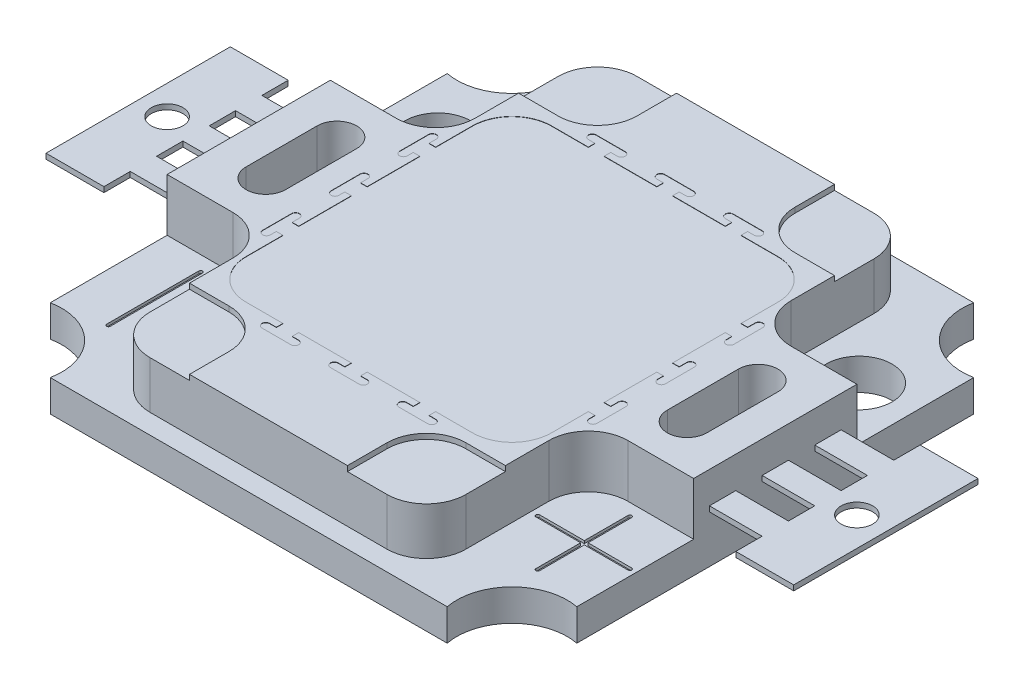
SolidWorks part; units mm, degrees
ref_plane "Front" through (0, 0, 0) normal (0, 0, 1) x (1, 0, 0)
ref_plane "Top" through (0, 0, 0) normal (0, 1, 0) x (1, 0, 0)
ref_plane "Right" through (0, 0, 0) normal (1, 0, 0) x (0, 0, -1)
sketch "Sketch1" plane through (0, 0, 0) normal (0, 1, 0) x (1, 0, 0)
  line L1 (0, 0) -> (20, 0)
  line L2 (0, 0) -> (0, 20)
  line L3 (0, 20) -> (20, 20)
  line L4 (20, 0) -> (20, 20)
  dimension "D1" = 20
  dimension "D2" = 20
extrude "Boss-Extrude1" add sketch "Sketch1" along normal blind 1.2
sketch "Sketch3" plane through (0, 1.2, 0) normal (0, 1, 0) x (1, 0, 0)
  line L0 (4, 19.25) -> (16, 0.75) construction
  line L1 (4, 19.25) -> (16, 19.25)
  line L2 (4, 19.25) -> (4, 13.1)
  line L3 (4, 0.75) -> (16, 0.75)
  line L4 (16, 19.25) -> (16, 13.1)
  line L5 (20, 20) -> (0, 0) construction
  line L6 (10, 10) -> (26, 10) construction
  line L7 (20, 0) -> (20, 20) construction
  line L8 (20, 6.9) -> (16, 6.9)
  line L9 (20, 6.9) -> (20, 13.1)
  line L10 (20, 13.1) -> (16, 13.1)
  line L11 (10, 10) -> (10, 16.9399) construction
  line L12 (16, 6.9) -> (20, 13.1) construction
  line L13 (16, 6.9) -> (16, 0.75)
  line L14 (0, 13.1) -> (4, 13.1)
  line L15 (0, 6.9) -> (0, 13.1)
  line L16 (0, 6.9) -> (4, 6.9)
  line L17 (4, 6.9) -> (4, 0.75)
  line L18 (18, 8.65) -> (18, 11.35) construction
  line L19 (18, 13.1) -> (18, 6.9) construction
  line L20 (17.25, 8.65) -> (17.25, 11.35)
  line L21 (18.75, 8.65) -> (18.75, 11.35)
  line L22 (16.5912, 12.1) -> (19.137, 12.1) construction
  line L23 (2, 8.65) -> (2, 11.35) construction
  line L24 (2.75, 8.65) -> (2.75, 11.35)
  line L25 (1.25, 8.65) -> (1.25, 11.35)
  line L26 (6, 4.95) -> (14, 15.05) construction
  line L27 (6, 15.05) -> (14, 15.05)
  line L28 (6, 15.05) -> (6, 4.95)
  line L29 (6, 4.95) -> (14, 4.95)
  line L30 (14, 15.05) -> (14, 4.95)
  arc A0 (17.25, 8.65) -> (18.75, 8.65) centre (18, 8.65) ccw
  arc A1 (18.75, 11.35) -> (17.25, 11.35) centre (18, 11.35) ccw
  arc A2 (2.75, 8.65) -> (1.25, 8.65) centre (2, 8.65) cw
  arc A3 (1.25, 11.35) -> (2.75, 11.35) centre (2, 11.35) cw
  point P8 (10, 10)
  point P17 (18, 10)
  point P27 (18, 10)
  point P36 (2, 10)
  dimension "D5" = 1
  dimension "D1" = 18.5
  dimension "D2" = 12
  dimension "D3" = 6.2
  dimension "D4" = 4.2
  dimension "D6" = 1.5
  dimension "D7" = 6
extrude "Boss-Extrude2" add sketch "Sketch3" along normal blind 2
sketch "Sketch4" plane through (0, 3.2, 0) normal (0, 1, 0) x (1, 0, 0)
  line L0 (20, 6.9) -> (20, 13.1) construction
  line L1 (4.2, 15.8) -> (15.8, 15.8)
  line L2 (4.2, 15.8) -> (4.2, 4.2)
  line L3 (4.2, 4.2) -> (15.8, 4.2)
  line L4 (15.8, 15.8) -> (15.8, 4.2)
  line L5 (0, 13.1) -> (0, 6.9) construction
  line L6 (0, 0) -> (20, 0) construction
  line L7 (20, 20) -> (0, 20) construction
  line L9 (4, 0.75) -> (7, 0.75)
  line L10 (4, 0.75) -> (4, 3.75)
  line L11 (4, 3.75) -> (7, 3.75)
  line L12 (7, 0.75) -> (7, 3.75)
  line L13 (16, 19.25) -> (13, 19.25)
  line L14 (16, 19.25) -> (16, 16.25)
  line L15 (16, 16.25) -> (13, 16.25)
  line L16 (13, 19.25) -> (13, 16.25)
  line L17 (4, 19.25) -> (7, 19.25)
  line L18 (4, 19.25) -> (4, 16.25)
  line L19 (4, 16.25) -> (7, 16.25)
  line L20 (7, 19.25) -> (7, 16.25)
  line L21 (16, 0.75) -> (13, 0.75)
  line L22 (16, 0.75) -> (16, 3.75)
  line L23 (16, 3.75) -> (13, 3.75)
  line L24 (13, 0.75) -> (13, 3.75)
  dimension "D1" = 4.2
  dimension "D2" = 4.2
  dimension "D3" = 4.2
  dimension "D4" = 4.2
  dimension "D5" = 3
fillet "Fillet1" radius 1.5 8 edges at (4, 2.2, -13.1) (4, 2.2, -6.9) (16, 2.2, -13.1) (16, 2.2, -6.9) (4, 2.2, -19.25) (16, 2.2, -19.25) (4, 2.2, -0.75) (16, 2.2, -0.75)
extrude "Cut-Extrude1" cut sketch "Sketch4" against normal blind 0.2
fillet "Fillet2" radius 1.5 8 edges at (13, 3.1, -16.25) (7, 3.1, -16.25) (7, 3.1, -3.75) (13, 3.1, -3.75) (15.8, 3.1, -4.2) (4.2, 3.1, -4.2) (4.2, 3.1, -15.8) (15.8, 3.1, -15.8)
sketch "Sketch5" plane through (0, 1.2, 0) normal (0, 1, 0) x (1, 0, 0)
  line L0 (20, 20) -> (0, 20) construction
  line L13 (0.4, 19.6) -> (19.6, 19.6) construction
  line L14 (0.4, 19.6) -> (0.4, 0.4) construction
  line L15 (0.4, 0.4) -> (19.6, 0.4) construction
  line L16 (19.6, 19.6) -> (19.6, 0.4) construction
  line L17 (20, 13.1) -> (20, 20) construction
  line L18 (0, 6.9) -> (0, 0) construction
  line L19 (0, 0) -> (20, 0) construction
  line L20 (2.5, 22.6773) -> (2.5, 16.8106) construction
  line L21 (0, 20) -> (0, 13.1) construction
  circle A0 centre (0.4, 19.6) radius 2.1
  dimension "D1" = 0.4
  dimension "D2" = 0.4
  dimension "D3" = 0.4
  dimension "D4" = 0.4
  dimension "D5" = 2.5
  dimension "D6" = 19.2
extrude "Cut-Extrude2" cut sketch "Sketch5" against normal through all
pattern_linear "LPattern1" count 2 spacing 19.2 along (1, 0, 0) count 2 spacing 19.2 along (0, 0, 1) of "Cut-Extrude2"
ref_plane "Plane1" through (0, 2, 0) normal (0, 1, 0) x (1, 0, 0)
sketch "Sketch6" plane through (0, 2, 0) normal (0, 1, 0) x (1, 0, 0)
  line L0 (20, 6.9) -> (20, 13.1) construction
  line L1 (22, 13.5) -> (24.2, 13.5)
  line L2 (22, 13.5) -> (22, 12.5)
  line L3 (22, 6.5) -> (24.2, 6.5)
  line L4 (24.2, 13.5) -> (24.2, 6.5)
  line L5 (20, 12.5) -> (22, 12.5)
  line L6 (20, 12.5) -> (20, 11.5)
  line L7 (20, 11.5) -> (22, 11.5)
  line L8 (22, 10.5) -> (22, 9.5) construction
  line L9 (22, 7.5) -> (22, 6.5)
  line L10 (20, 10.5) -> (22, 10.5)
  line L11 (20, 10.5) -> (20, 9.5)
  line L12 (20, 9.5) -> (22, 9.5)
  line L13 (22, 11.5) -> (22, 10.5)
  line L14 (20, 8.5) -> (22, 8.5)
  line L15 (20, 8.5) -> (20, 7.5)
  line L16 (20, 7.5) -> (22, 7.5)
  line L17 (22, 9.5) -> (22, 8.5)
  line L18 (20, 10) -> (24.2, 10) construction
  line L19 (10, 0.75) -> (10, 19.25) construction
  line L20 (5.5, 0.75) -> (14.5, 0.75) construction
  line L21 (13, 19.25) -> (7, 19.25) construction
  line L22 (23.1, 13.5) -> (23.1, 6.5) construction
  line L23 (-3.1, 13.5) -> (-3.1, 6.5) construction
  line L24 (0, 10) -> (-4.2, 10) construction
  line L25 (-2, 10.5) -> (-2, 9.5) construction
  line L26 (-2, 9.5) -> (-2, 8.5)
  line L27 (0, 7.5) -> (-2, 7.5)
  line L28 (0, 8.5) -> (0, 7.5)
  line L29 (0, 8.5) -> (-2, 8.5)
  line L30 (-2, 11.5) -> (-2, 10.5)
  line L31 (0, 9.5) -> (-2, 9.5)
  line L32 (0, 10.5) -> (0, 9.5)
  line L33 (0, 10.5) -> (-2, 10.5)
  line L34 (-2, 7.5) -> (-2, 6.5)
  line L35 (0, 11.5) -> (-2, 11.5)
  line L36 (0, 12.5) -> (0, 11.5)
  line L37 (0, 12.5) -> (-2, 12.5)
  line L38 (-4.2, 13.5) -> (-4.2, 6.5)
  line L39 (-2, 6.5) -> (-4.2, 6.5)
  line L40 (-2, 13.5) -> (-2, 12.5)
  line L41 (-2, 13.5) -> (-4.2, 13.5)
  circle A0 centre (23.1, 10) radius 0.6
  circle A1 centre (-3.1, 10) radius 0.6
  dimension "D9" = 1.2
  dimension "D1" = 7
  dimension "D2" = 2.2
  dimension "D3" = 2
  dimension "D4" = 1
  dimension "D5" = 1
  dimension "D6" = 1
  dimension "D7" = 1
  dimension "D8" = 1
extrude "Boss-Extrude3" add sketch "Sketch6" against normal blind 0.2
sketch "Sketch7" plane through (0, 3.2, 0) normal (0, 1, 0) x (1, 0, 0)
  line L0 (4.7825, 3.8) -> (14.632, 3.8) construction
  line L1 (5.7, 4.2) -> (14.3, 4.2) construction
  line L2 (9.45, 3.8) -> (10.55, 3.8) construction
  line L3 (9.45, 3.95) -> (9.7, 3.95)
  line L4 (9.45, 3.65) -> (10.55, 3.65)
  line L5 (9.3, 4.0517) -> (9.3, 3.1833) construction
  line L6 (10.7, 4.0517) -> (10.7, 3.1833) construction
  line L7 (10, 4.2) -> (10, 3.4) construction
  line L8 (12.05, 3.95) -> (12.3, 3.95)
  line L9 (12.05, 3.65) -> (13.15, 3.65)
  line L10 (5.7, 4.2) -> (14.3, 4.2) construction
  line L11 (12.9, 4.2) -> (12.3, 4.2)
  line L12 (12.9, 4.2) -> (12.9, 3.95)
  line L13 (12.3, 4.2) -> (12.3, 3.95)
  line L14 (12.9, 3.95) -> (13.15, 3.95)
  line L15 (12.05, 3.8) -> (13.15, 3.8) construction
  line L16 (6.85, 3.95) -> (7.1, 3.95)
  line L17 (6.85, 3.65) -> (7.95, 3.65)
  line L18 (7.7, 4.2) -> (7.1, 4.2)
  line L19 (7.7, 4.2) -> (7.7, 3.95)
  line L20 (10.3, 4.2) -> (9.7, 4.2)
  line L21 (10.3, 4.2) -> (10.3, 3.95)
  line L22 (7.1, 4.2) -> (7.1, 3.95)
  line L23 (9.7, 4.2) -> (9.7, 3.95)
  line L24 (10.3, 3.95) -> (10.55, 3.95)
  line L25 (7.7, 3.95) -> (7.95, 3.95)
  line L26 (6.85, 3.8) -> (7.95, 3.8) construction
  line L27 (6, 10) -> (14, 10) construction
  line L28 (6, 15.05) -> (6, 4.95) construction
  line L29 (14, 4.95) -> (14, 15.05) construction
  line L30 (6.85, 16.2) -> (7.95, 16.2) construction
  line L31 (12.05, 16.2) -> (13.15, 16.2) construction
  line L32 (10, 15.8) -> (10, 16.6) construction
  line L33 (10.7, 15.9483) -> (10.7, 16.8167) construction
  line L34 (9.3, 15.9483) -> (9.3, 16.8167) construction
  line L35 (9.45, 16.2) -> (10.55, 16.2) construction
  line L36 (7.7, 16.05) -> (7.95, 16.05)
  line L37 (10.3, 16.05) -> (10.55, 16.05)
  line L38 (9.7, 15.8) -> (9.7, 16.05)
  line L39 (7.1, 15.8) -> (7.1, 16.05)
  line L40 (10.3, 15.8) -> (10.3, 16.05)
  line L41 (10.3, 15.8) -> (9.7, 15.8)
  line L42 (7.7, 15.8) -> (7.7, 16.05)
  line L43 (7.7, 15.8) -> (7.1, 15.8)
  line L44 (6.85, 16.35) -> (7.95, 16.35)
  line L45 (6.85, 16.05) -> (7.1, 16.05)
  line L46 (12.9, 16.05) -> (13.15, 16.05)
  line L47 (12.3, 15.8) -> (12.3, 16.05)
  line L48 (12.9, 15.8) -> (12.9, 16.05)
  line L49 (12.9, 15.8) -> (12.3, 15.8)
  line L50 (12.05, 16.35) -> (13.15, 16.35)
  line L51 (12.05, 16.05) -> (12.3, 16.05)
  line L52 (9.45, 16.35) -> (10.55, 16.35)
  line L53 (9.45, 16.05) -> (9.7, 16.05)
  arc A0 (9.45, 3.95) -> (9.45, 3.65) centre (9.45, 3.8) ccw
  arc A1 (10.55, 3.65) -> (10.55, 3.95) centre (10.55, 3.8) ccw
  arc A2 (12.05, 3.95) -> (12.05, 3.65) centre (12.05, 3.8) ccw
  arc A3 (13.15, 3.65) -> (13.15, 3.95) centre (13.15, 3.8) ccw
  arc A4 (6.85, 3.95) -> (6.85, 3.65) centre (6.85, 3.8) ccw
  arc A5 (7.95, 3.65) -> (7.95, 3.95) centre (7.95, 3.8) ccw
  arc A6 (7.95, 16.35) -> (7.95, 16.05) centre (7.95, 16.2) cw
  arc A7 (6.85, 16.05) -> (6.85, 16.35) centre (6.85, 16.2) cw
  arc A8 (13.15, 16.35) -> (13.15, 16.05) centre (13.15, 16.2) cw
  arc A9 (12.05, 16.05) -> (12.05, 16.35) centre (12.05, 16.2) cw
  arc A10 (10.55, 16.35) -> (10.55, 16.05) centre (10.55, 16.2) cw
  arc A11 (9.45, 16.05) -> (9.45, 16.35) centre (9.45, 16.2) cw
  point P6 (10, 3.8)
  point P22 (12.6, 3.8)
  point P35 (7.4, 3.8)
  point P87 (7.4, 16.2)
  point P88 (12.6, 16.2)
  point P89 (10, 16.2)
  dimension "D1" = 0.4
  dimension "D2" = 0.3
  dimension "D3" = 1.4
  dimension "D6" = 0.6
sketch "Sketch8" plane through (0, 3.2, 0) normal (0, 1, 0) x (1, 0, 0)
  line L0 (10, 15.05) -> (10, 4.95) construction
  line L1 (14, 15.05) -> (6, 15.05) construction
  line L2 (6, 4.95) -> (14, 4.95) construction
  line L3 (3.8, 14.7064) -> (3.8, 5.2936) construction
  line L4 (4.2, 14.3) -> (4.2, 5.7) construction
  line L5 (3.8, 10) -> (4.825, 10) construction
  line L6 (6, 10) -> (14, 10) construction
  line L7 (3.9476, 6.85) -> (3.95, 7.1)
  line L8 (4.2, 7.1) -> (3.95, 7.1)
  line L9 (4.2, 7.7) -> (3.95, 7.7)
  line L10 (3.9476, 9.45) -> (3.95, 9.7)
  line L11 (4.2, 9.7) -> (3.95, 9.7)
  line L12 (4.2, 10.3) -> (3.95, 10.3)
  line L13 (4.2, 10.3) -> (4.2, 9.7)
  line L14 (3.95, 10.3) -> (3.9475, 10.55)
  line L15 (4.2, 7.7) -> (4.2, 7.1)
  line L16 (3.95, 7.7) -> (3.9475, 7.95)
  line L17 (3.65, 9.477) -> (3.65, 10.577)
  line L18 (3.65, 6.877) -> (3.65, 7.977)
  line L19 (3.8, 7.4) -> (4.825, 7.4) construction
  line L20 (3.9476, 12.05) -> (3.95, 12.3)
  line L21 (4.2, 12.3) -> (3.95, 12.3)
  line L22 (4.2, 12.9) -> (3.95, 12.9)
  line L23 (4.2, 12.9) -> (4.2, 12.3)
  line L24 (3.95, 12.9) -> (3.9475, 13.15)
  line L25 (3.65, 12.077) -> (3.65, 13.177)
  line L26 (3.8, 12.6) -> (4.825, 12.6) construction
  line L27 (16.2, 12.6) -> (15.175, 12.6) construction
  line L28 (16.2, 7.4) -> (15.175, 7.4) construction
  line L29 (16.2, 10) -> (15.175, 10) construction
  line L30 (16.2, 14.7064) -> (16.2, 5.2936) construction
  line L31 (16.35, 12.077) -> (16.35, 13.177)
  line L32 (16.05, 12.9) -> (16.0525, 13.15)
  line L33 (15.8, 12.9) -> (15.8, 12.3)
  line L34 (15.8, 12.9) -> (16.05, 12.9)
  line L35 (15.8, 12.3) -> (16.05, 12.3)
  line L36 (16.0524, 12.05) -> (16.05, 12.3)
  line L37 (16.35, 6.877) -> (16.35, 7.977)
  line L38 (16.35, 9.477) -> (16.35, 10.577)
  line L39 (16.05, 7.7) -> (16.0525, 7.95)
  line L40 (15.8, 7.7) -> (15.8, 7.1)
  line L41 (16.05, 10.3) -> (16.0525, 10.55)
  line L42 (15.8, 10.3) -> (15.8, 9.7)
  line L43 (15.8, 10.3) -> (16.05, 10.3)
  line L44 (15.8, 9.7) -> (16.05, 9.7)
  line L45 (16.0524, 9.45) -> (16.05, 9.7)
  line L46 (15.8, 7.7) -> (16.05, 7.7)
  line L47 (15.8, 7.1) -> (16.05, 7.1)
  line L48 (16.0524, 6.85) -> (16.05, 7.1)
  arc A0 (3.9475, 7.95) -> (3.65, 7.977) centre (3.8, 7.977) ccw
  arc A1 (3.65, 6.877) -> (3.9476, 6.85) centre (3.8, 6.877) ccw
  arc A2 (3.9475, 10.55) -> (3.65, 10.577) centre (3.8, 10.577) ccw
  arc A3 (3.65, 9.477) -> (3.9476, 9.45) centre (3.8, 9.477) ccw
  arc A4 (3.9475, 13.15) -> (3.65, 13.177) centre (3.8, 13.177) ccw
  arc A5 (3.65, 12.077) -> (3.9476, 12.05) centre (3.8, 12.077) ccw
  arc A6 (16.35, 12.077) -> (16.0524, 12.05) centre (16.2, 12.077) cw
  arc A7 (16.0525, 13.15) -> (16.35, 13.177) centre (16.2, 13.177) cw
  arc A8 (16.35, 9.477) -> (16.0524, 9.45) centre (16.2, 9.477) cw
  arc A9 (16.0525, 10.55) -> (16.35, 10.577) centre (16.2, 10.577) cw
  arc A10 (16.35, 6.877) -> (16.0524, 6.85) centre (16.2, 6.877) cw
  arc A11 (16.0525, 7.95) -> (16.35, 7.977) centre (16.2, 7.977) cw
  point P10 (4.2, 10)
  point P37 (4.2, 7.4)
  point P49 (4.2, 12.6)
  point P89 (15.8, 12.6)
  point P90 (15.8, 7.4)
  point P91 (15.8, 10)
  dimension "D6" = 0.15
  dimension "D7" = 0.15
  dimension "D1" = 0.4
  dimension "D2" = 0.6
  dimension "D3" = 0.25
  dimension "D4" = 0.25
  dimension "D5" = 1.1
  dimension "D8" = 1.1
  dimension "D9" = 0.25
  dimension "D10" = 0.25
  dimension "D11" = 0.4
  dimension "D12" = 2
  dimension "D13" = 2
extrude "Cut-Extrude3" cut sketch "Sketch7" against normal blind 0.2
extrude "Cut-Extrude4" cut sketch "Sketch8" against normal blind 0.2
sketch "Sketch9" plane through (0, 1.2, 0) normal (0, 1, 0) x (1, 0, 0)
  line L1 (6, 15.05) -> (14, 15.05)
  line L2 (6, 15.05) -> (6, 4.95)
  line L3 (6, 4.95) -> (14, 4.95)
  line L4 (14, 15.05) -> (14, 4.95)
extrude "Boss-Extrude4" add sketch "Sketch9" along normal blind 1.8 separate body
sketch "Sketch10" plane through (0, 3, 0) normal (0, 1, 0) x (1, 0, 0)
  line L76 (5.7, 4.2) -> (7.1, 4.2)
  line L77 (7.1, 4.2) -> (7.1, 3.95)
  line L78 (7.1, 3.95) -> (6.85, 3.95)
  line L79 (6.85, 3.65) -> (7.95, 3.65)
  line L80 (7.95, 3.95) -> (7.7, 3.95)
  line L81 (7.7, 3.95) -> (7.7, 4.2)
  line L82 (7.7, 4.2) -> (9.7, 4.2)
  line L83 (9.7, 4.2) -> (9.7, 3.95)
  line L84 (9.7, 3.95) -> (9.45, 3.95)
  line L85 (9.45, 3.65) -> (10.55, 3.65)
  line L86 (10.55, 3.95) -> (10.3, 3.95)
  line L87 (10.3, 3.95) -> (10.3, 4.2)
  line L88 (10.3, 4.2) -> (12.3, 4.2)
  line L89 (12.3, 4.2) -> (12.3, 3.95)
  line L90 (12.3, 3.95) -> (12.05, 3.95)
  line L91 (12.05, 3.65) -> (13.15, 3.65)
  line L92 (13.15, 3.95) -> (12.9, 3.95)
  line L93 (12.9, 3.95) -> (12.9, 4.2)
  line L94 (12.9, 4.2) -> (14.3, 4.2)
  line L95 (15.8, 5.7) -> (15.8, 7.1)
  line L96 (15.8, 7.1) -> (16.05, 7.1)
  line L97 (16.05, 7.1) -> (16.0524, 6.85)
  line L98 (16.35, 6.877) -> (16.35, 7.977)
  line L99 (16.0525, 7.95) -> (16.05, 7.7)
  line L100 (16.05, 7.7) -> (15.8, 7.7)
  line L101 (15.8, 7.7) -> (15.8, 9.7)
  line L102 (15.8, 9.7) -> (16.05, 9.7)
  line L103 (16.05, 9.7) -> (16.0524, 9.45)
  line L104 (16.35, 9.477) -> (16.35, 10.577)
  line L105 (16.0525, 10.55) -> (16.05, 10.3)
  line L106 (16.05, 10.3) -> (15.8, 10.3)
  line L107 (15.8, 10.3) -> (15.8, 12.3)
  line L108 (15.8, 12.3) -> (16.05, 12.3)
  line L109 (16.05, 12.3) -> (16.0524, 12.05)
  line L110 (16.35, 12.077) -> (16.35, 13.177)
  line L111 (16.0525, 13.15) -> (16.05, 12.9)
  line L112 (16.05, 12.9) -> (15.8, 12.9)
  line L113 (15.8, 12.9) -> (15.8, 14.3)
  line L114 (14.3, 15.8) -> (12.9, 15.8)
  line L115 (12.9, 15.8) -> (12.9, 16.05)
  line L116 (12.9, 16.05) -> (13.15, 16.05)
  line L117 (13.15, 16.35) -> (12.05, 16.35)
  line L118 (12.05, 16.05) -> (12.3, 16.05)
  line L119 (12.3, 16.05) -> (12.3, 15.8)
  line L120 (12.3, 15.8) -> (10.3, 15.8)
  line L121 (10.3, 15.8) -> (10.3, 16.05)
  line L122 (10.3, 16.05) -> (10.55, 16.05)
  line L123 (10.55, 16.35) -> (9.45, 16.35)
  line L124 (9.45, 16.05) -> (9.7, 16.05)
  line L125 (9.7, 16.05) -> (9.7, 15.8)
  line L126 (9.7, 15.8) -> (7.7, 15.8)
  line L127 (7.7, 15.8) -> (7.7, 16.05)
  line L128 (7.7, 16.05) -> (7.95, 16.05)
  line L129 (7.95, 16.35) -> (6.85, 16.35)
  line L130 (6.85, 16.05) -> (7.1, 16.05)
  line L131 (7.1, 16.05) -> (7.1, 15.8)
  line L132 (7.1, 15.8) -> (5.7, 15.8)
  line L133 (4.2, 14.3) -> (4.2, 12.9)
  line L134 (4.2, 12.9) -> (3.95, 12.9)
  line L135 (3.95, 12.9) -> (3.9475, 13.15)
  line L136 (3.65, 13.177) -> (3.65, 12.077)
  line L137 (3.9476, 12.05) -> (3.95, 12.3)
  line L138 (3.95, 12.3) -> (4.2, 12.3)
  line L139 (4.2, 12.3) -> (4.2, 10.3)
  line L140 (4.2, 10.3) -> (3.95, 10.3)
  line L141 (3.95, 10.3) -> (3.9475, 10.55)
  line L142 (3.65, 10.577) -> (3.65, 9.477)
  line L143 (3.9476, 9.45) -> (3.95, 9.7)
  line L144 (3.95, 9.7) -> (4.2, 9.7)
  line L145 (4.2, 9.7) -> (4.2, 7.7)
  line L146 (4.2, 7.7) -> (3.95, 7.7)
  line L147 (3.95, 7.7) -> (3.9475, 7.95)
  line L148 (3.65, 7.977) -> (3.65, 6.877)
  line L149 (3.9476, 6.85) -> (3.95, 7.1)
  line L150 (3.95, 7.1) -> (4.2, 7.1)
  line L151 (4.2, 7.1) -> (4.2, 5.7)
  line L152 (5.7, 4.2) -> (7.1, 4.2)
  line L153 (7.1, 4.2) -> (7.1, 3.95)
  line L154 (7.1, 3.95) -> (6.85, 3.95)
  line L155 (6.85, 3.65) -> (7.95, 3.65)
  line L156 (7.95, 3.95) -> (7.7, 3.95)
  line L157 (7.7, 3.95) -> (7.7, 4.2)
  line L158 (7.7, 4.2) -> (9.7, 4.2)
  line L159 (9.7, 4.2) -> (9.7, 3.95)
  line L160 (9.7, 3.95) -> (9.45, 3.95)
  line L161 (9.45, 3.65) -> (10.55, 3.65)
  line L162 (10.55, 3.95) -> (10.3, 3.95)
  line L163 (10.3, 3.95) -> (10.3, 4.2)
  line L164 (10.3, 4.2) -> (12.3, 4.2)
  line L165 (12.3, 4.2) -> (12.3, 3.95)
  line L166 (12.3, 3.95) -> (12.05, 3.95)
  line L167 (12.05, 3.65) -> (13.15, 3.65)
  line L168 (13.15, 3.95) -> (12.9, 3.95)
  line L169 (12.9, 3.95) -> (12.9, 4.2)
  line L170 (12.9, 4.2) -> (14.3, 4.2)
  line L171 (15.8, 5.7) -> (15.8, 7.1)
  line L172 (15.8, 7.1) -> (16.05, 7.1)
  line L173 (16.05, 7.1) -> (16.0524, 6.85)
  line L174 (16.35, 6.877) -> (16.35, 7.977)
  line L175 (16.0525, 7.95) -> (16.05, 7.7)
  line L176 (16.05, 7.7) -> (15.8, 7.7)
  line L177 (15.8, 7.7) -> (15.8, 9.7)
  line L178 (15.8, 9.7) -> (16.05, 9.7)
  line L179 (16.05, 9.7) -> (16.0524, 9.45)
  line L180 (16.35, 9.477) -> (16.35, 10.577)
  line L181 (16.0525, 10.55) -> (16.05, 10.3)
  line L182 (16.05, 10.3) -> (15.8, 10.3)
  line L183 (15.8, 10.3) -> (15.8, 12.3)
  line L184 (15.8, 12.3) -> (16.05, 12.3)
  line L185 (16.05, 12.3) -> (16.0524, 12.05)
  line L186 (16.35, 12.077) -> (16.35, 13.177)
  line L187 (16.0525, 13.15) -> (16.05, 12.9)
  line L188 (16.05, 12.9) -> (15.8, 12.9)
  line L189 (15.8, 12.9) -> (15.8, 14.3)
  line L190 (14.3, 15.8) -> (12.9, 15.8)
  line L191 (12.9, 15.8) -> (12.9, 16.05)
  line L192 (12.9, 16.05) -> (13.15, 16.05)
  line L193 (13.15, 16.35) -> (12.05, 16.35)
  line L194 (12.05, 16.05) -> (12.3, 16.05)
  line L195 (12.3, 16.05) -> (12.3, 15.8)
  line L196 (12.3, 15.8) -> (10.3, 15.8)
  line L197 (10.3, 15.8) -> (10.3, 16.05)
  line L198 (10.3, 16.05) -> (10.55, 16.05)
  line L199 (10.55, 16.35) -> (9.45, 16.35)
  line L200 (9.45, 16.05) -> (9.7, 16.05)
  line L201 (9.7, 16.05) -> (9.7, 15.8)
  line L202 (9.7, 15.8) -> (7.7, 15.8)
  line L203 (7.7, 15.8) -> (7.7, 16.05)
  line L204 (7.7, 16.05) -> (7.95, 16.05)
  line L205 (7.95, 16.35) -> (6.85, 16.35)
  line L206 (6.85, 16.05) -> (7.1, 16.05)
  line L207 (7.1, 16.05) -> (7.1, 15.8)
  line L208 (7.1, 15.8) -> (5.7, 15.8)
  line L209 (4.2, 14.3) -> (4.2, 12.9)
  line L210 (4.2, 12.9) -> (3.95, 12.9)
  line L211 (3.95, 12.9) -> (3.9475, 13.15)
  line L212 (3.65, 13.177) -> (3.65, 12.077)
  line L213 (3.9476, 12.05) -> (3.95, 12.3)
  line L214 (3.95, 12.3) -> (4.2, 12.3)
  line L215 (4.2, 12.3) -> (4.2, 10.3)
  line L216 (4.2, 10.3) -> (3.95, 10.3)
  line L217 (3.95, 10.3) -> (3.9475, 10.55)
  line L218 (3.65, 10.577) -> (3.65, 9.477)
  line L219 (3.9476, 9.45) -> (3.95, 9.7)
  line L220 (3.95, 9.7) -> (4.2, 9.7)
  line L221 (4.2, 9.7) -> (4.2, 7.7)
  line L222 (4.2, 7.7) -> (3.95, 7.7)
  line L223 (3.95, 7.7) -> (3.9475, 7.95)
  line L224 (3.65, 7.977) -> (3.65, 6.877)
  line L225 (3.9476, 6.85) -> (3.95, 7.1)
  line L226 (3.95, 7.1) -> (4.2, 7.1)
  line L227 (4.2, 7.1) -> (4.2, 5.7)
  arc A28 (6.85, 3.95) -> (6.85, 3.65) centre (6.85, 3.8) ccw
  arc A29 (7.95, 3.65) -> (7.95, 3.95) centre (7.95, 3.8) ccw
  arc A30 (9.45, 3.95) -> (9.45, 3.65) centre (9.45, 3.8) ccw
  arc A31 (10.55, 3.65) -> (10.55, 3.95) centre (10.55, 3.8) ccw
  arc A32 (12.05, 3.95) -> (12.05, 3.65) centre (12.05, 3.8) ccw
  arc A33 (13.15, 3.65) -> (13.15, 3.95) centre (13.15, 3.8) ccw
  arc A34 (14.3, 4.2) -> (15.8, 5.7) centre (14.3, 5.7) ccw
  arc A35 (16.0524, 6.85) -> (16.35, 6.877) centre (16.2, 6.877) ccw
  arc A36 (16.35, 7.977) -> (16.0525, 7.95) centre (16.2, 7.977) ccw
  arc A37 (16.0524, 9.45) -> (16.35, 9.477) centre (16.2, 9.477) ccw
  arc A38 (16.35, 10.577) -> (16.0525, 10.55) centre (16.2, 10.577) ccw
  arc A39 (16.0524, 12.05) -> (16.35, 12.077) centre (16.2, 12.077) ccw
  arc A40 (16.35, 13.177) -> (16.0525, 13.15) centre (16.2, 13.177) ccw
  arc A41 (15.8, 14.3) -> (14.3, 15.8) centre (14.3, 14.3) ccw
  arc A42 (13.15, 16.05) -> (13.15, 16.35) centre (13.15, 16.2) ccw
  arc A43 (12.05, 16.35) -> (12.05, 16.05) centre (12.05, 16.2) ccw
  arc A44 (10.55, 16.05) -> (10.55, 16.35) centre (10.55, 16.2) ccw
  arc A45 (9.45, 16.35) -> (9.45, 16.05) centre (9.45, 16.2) ccw
  arc A46 (7.95, 16.05) -> (7.95, 16.35) centre (7.95, 16.2) ccw
  arc A47 (6.85, 16.35) -> (6.85, 16.05) centre (6.85, 16.2) ccw
  arc A48 (5.7, 15.8) -> (4.2, 14.3) centre (5.7, 14.3) ccw
  arc A49 (3.9475, 13.15) -> (3.65, 13.177) centre (3.8, 13.177) ccw
  arc A50 (3.65, 12.077) -> (3.9476, 12.05) centre (3.8, 12.077) ccw
  arc A51 (3.9475, 10.55) -> (3.65, 10.577) centre (3.8, 10.577) ccw
  arc A52 (3.65, 9.477) -> (3.9476, 9.45) centre (3.8, 9.477) ccw
  arc A53 (3.9475, 7.95) -> (3.65, 7.977) centre (3.8, 7.977) ccw
  arc A54 (3.65, 6.877) -> (3.9476, 6.85) centre (3.8, 6.877) ccw
  arc A55 (4.2, 5.7) -> (5.7, 4.2) centre (5.7, 5.7) ccw
  arc A56 (6.85, 3.95) -> (6.85, 3.65) centre (6.85, 3.8) ccw
  arc A57 (7.95, 3.65) -> (7.95, 3.95) centre (7.95, 3.8) ccw
  arc A58 (9.45, 3.95) -> (9.45, 3.65) centre (9.45, 3.8) ccw
  arc A59 (10.55, 3.65) -> (10.55, 3.95) centre (10.55, 3.8) ccw
  arc A60 (12.05, 3.95) -> (12.05, 3.65) centre (12.05, 3.8) ccw
  arc A61 (13.15, 3.65) -> (13.15, 3.95) centre (13.15, 3.8) ccw
  arc A62 (14.3, 4.2) -> (15.8, 5.7) centre (14.3, 5.7) ccw
  arc A63 (16.0524, 6.85) -> (16.35, 6.877) centre (16.2, 6.877) ccw
  arc A64 (16.35, 7.977) -> (16.0525, 7.95) centre (16.2, 7.977) ccw
  arc A65 (16.0524, 9.45) -> (16.35, 9.477) centre (16.2, 9.477) ccw
  arc A66 (16.35, 10.577) -> (16.0525, 10.55) centre (16.2, 10.577) ccw
  arc A67 (16.0524, 12.05) -> (16.35, 12.077) centre (16.2, 12.077) ccw
  arc A68 (16.35, 13.177) -> (16.0525, 13.15) centre (16.2, 13.177) ccw
  arc A69 (15.8, 14.3) -> (14.3, 15.8) centre (14.3, 14.3) ccw
  arc A70 (13.15, 16.05) -> (13.15, 16.35) centre (13.15, 16.2) ccw
  arc A71 (12.05, 16.35) -> (12.05, 16.05) centre (12.05, 16.2) ccw
  arc A72 (10.55, 16.05) -> (10.55, 16.35) centre (10.55, 16.2) ccw
  arc A73 (9.45, 16.35) -> (9.45, 16.05) centre (9.45, 16.2) ccw
  arc A74 (7.95, 16.05) -> (7.95, 16.35) centre (7.95, 16.2) ccw
  arc A75 (6.85, 16.35) -> (6.85, 16.05) centre (6.85, 16.2) ccw
  arc A76 (5.7, 15.8) -> (4.2, 14.3) centre (5.7, 14.3) ccw
  arc A77 (3.9475, 13.15) -> (3.65, 13.177) centre (3.8, 13.177) ccw
  arc A78 (3.65, 12.077) -> (3.9476, 12.05) centre (3.8, 12.077) ccw
  arc A79 (3.9475, 10.55) -> (3.65, 10.577) centre (3.8, 10.577) ccw
  arc A80 (3.65, 9.477) -> (3.9476, 9.45) centre (3.8, 9.477) ccw
  arc A81 (3.9475, 7.95) -> (3.65, 7.977) centre (3.8, 7.977) ccw
  arc A82 (3.65, 6.877) -> (3.9476, 6.85) centre (3.8, 6.877) ccw
  arc A83 (4.2, 5.7) -> (5.7, 4.2) centre (5.7, 5.7) ccw
  dimension "D1" = 0
extrude "Boss-Extrude5" add sketch "Sketch10" along normal blind 0.19 separate body
sketch "Sketch11" plane through (0, 1.2, 0) normal (0, 1, 0) x (1, 0, 0)
  line L0 (2, 15.1826) -> (20.8112, 15.1826) construction
  line L1 (4, 17.75) -> (4, 14.6) construction
  line L2 (16, 14.6) -> (16, 16.25) construction
  circle A0 centre (2, 15.1826) radius 1.25
  circle A1 centre (18, 15.1826) radius 1.25
  dimension "D1" = 2.5
  dimension "D2" = 2
  dimension "D3" = 2
extrude "Cut-Extrude5" cut sketch "Sketch11" against normal through all
sketch "Sketch12" plane through (0, 1.2, 0) normal (0, 1, 0) x (1, 0, 0)
  line L0 (18.0389, 6.4385) -> (18.0389, 2.9385) construction
  line L1 (18.1089, 6.4385) -> (18.1089, 4.7785)
  line L2 (17.9689, 6.4385) -> (17.9689, 4.7785)
  line L3 (16.2689, 4.7085) -> (19.7689, 4.7085) construction
  line L4 (16.2689, 4.7785) -> (17.9689, 4.7785)
  line L5 (16.2689, 4.6385) -> (17.9689, 4.6385)
  line L6 (1.8463, 6.3252) -> (1.8463, 2.8252) construction
  line L7 (1.9163, 6.3252) -> (1.9163, 2.8252)
  line L8 (1.7763, 6.3252) -> (1.7763, 2.8252)
  line L9 (17.9689, 4.6385) -> (17.9689, 2.9385)
  line L10 (18.1089, 4.7785) -> (19.7689, 4.7785)
  line L11 (18.1089, 4.6385) -> (18.1089, 2.9385)
  line L12 (18.1089, 4.6385) -> (19.7689, 4.6385)
  arc A0 (18.1089, 6.4385) -> (17.9689, 6.4385) centre (18.0389, 6.4385) ccw
  arc A1 (17.9689, 2.9385) -> (18.1089, 2.9385) centre (18.0389, 2.9385) ccw
  arc A2 (16.2689, 4.7785) -> (16.2689, 4.6385) centre (16.2689, 4.7085) ccw
  arc A3 (19.7689, 4.6385) -> (19.7689, 4.7785) centre (19.7689, 4.7085) ccw
  arc A4 (1.9163, 6.3252) -> (1.7763, 6.3252) centre (1.8463, 6.3252) ccw
  arc A5 (1.7763, 2.8252) -> (1.9163, 2.8252) centre (1.8463, 2.8252) ccw
  point P2 (18.0189, 4.6885)
  point P9 (18.0389, 4.6885)
  point P16 (1.8463, 4.5752)
  point P21 (22.3635, 3.891)
  dimension "D1" = 3.5
  dimension "D2" = 3.5
  dimension "D3" = 0.14
  dimension "D4" = 0.14
  dimension "D5" = 0.14
extrude "Cut-Extrude6" cut sketch "Sketch12" against normal blind 0.1
ref_plane "Plan1" through (10, 0, 0) normal (1, 0, 0) x (0, 0, -1)
ref_plane "Plan2" through (0, 0, -10) normal (0, 0, 1) x (1, 0, 0)
ref_axis "Axe1" through (10, 9.4255, -10) along (0, -1, 0)
